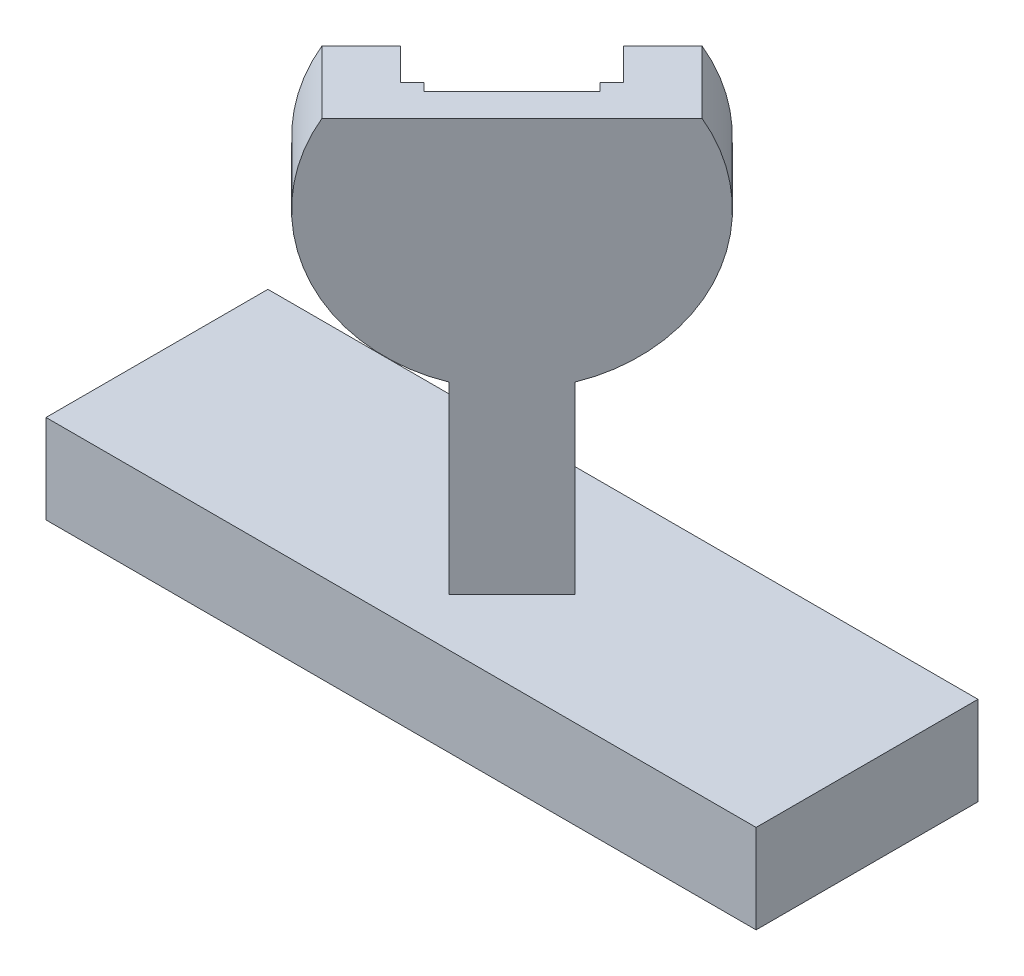
SolidWorks part; units mm, degrees
ref_plane "Front Plane" through (0, 0, 0) normal (0, 0, 1) x (1, 0, 0)
ref_plane "Top Plane" through (0, 0, 0) normal (0, 1, 0) x (1, 0, 0)
ref_plane "Right Plane" through (0, 0, 0) normal (1, 0, 0) x (0, 0, -1)
sketch "Sketch1" plane through (0, 0, 0) normal (0, 1, 0) x (1, 0, 0)
  line L0 (0, 7.1842) -> (-7.1842, 0)
  line L3 (-40.64, 12.7) -> (40.64, 12.7)
  line L4 (-40.64, 12.7) -> (-40.64, -12.7)
  line L5 (-40.64, -12.7) -> (40.64, -12.7)
  line L6 (40.64, 12.7) -> (40.64, -12.7)
  line L7 (-40.64, 12.7) -> (40.64, -12.7) construction
  line L8 (-40.64, -12.7) -> (40.64, 12.7) construction
  line L9 (-7.1842, 0) -> (0, -7.1842)
  line L10 (0, -7.1842) -> (7.1842, 0)
  line L11 (7.1842, 0) -> (0, 7.1842)
  line L12 (-7.1842, 0) -> (7.1842, 0) construction
  point P0 (0, 0)
  point P2 (0, 0)
  point P9 (0, 0)
  dimension "D1" = 81.28
  dimension "D2" = 25.4
  dimension "D3" = 10.16
extrude "Boss-Extrude1" add sketch "Sketch1" against normal blind 10.16 contours L10 L11 L0 L9 | L6 L3 L4 L5 L11 L10 L9 L0 region at (0, 0, 0) region at (0, 0, -11.8484)
extrude "Boss-Extrude2" add sketch "Sketch1<3>" along normal blind 25.4 contours L10 L11 L0 L9 region at (0, 0, 0)
sketch "Sketch1<3>" plane through (0, 0, 0) normal (0, 1, 0) x (1, 0, 0) same geometry as "Sketch1"
ref_plane "Plane1" through (3.5921, 0, 3.5921) normal (0.7071, 0, 0.7071) x (0.7071, 0, -0.7071)
sketch "Sketch3" plane through (3.5921, 0, 3.5921) normal (0.7071, 0, 0.7071) x (0.7071, 0, -0.7071)
  line L0 (-5.08, 25.4) -> (5.08, 25.4) construction
  line L1 (-5.08, 25.4) -> (5.08, 25.4)
  line L2 (0, 0) -> (0, 38.1635) construction
  line L3 (-9.0252, 47.1887) -> (0, 38.1635) construction
  line L4 (0, 38.1635) -> (9.0252, 47.1887) construction
  line L5 (-9.0252, 47.1887) -> (15.3928, 47.1887)
  line L6 (15.3928, 47.1887) -> (-15.3928, 47.1887)
  arc A0 (-9.0252, 47.1887) -> (9.0252, 47.1887) centre (0, 38.1635) ccw
  arc A1 (-15.3928, 47.1887) -> (15.3928, 47.1887) centre (0, 38.1635) ccw
  arc A2 (-12.6173, 50.7808) -> (12.6173, 50.7808) centre (0, 38.1635) ccw construction
  arc A3 (-7.1167, 47.1887) -> (7.1167, 47.1887) centre (0, 38.1635) ccw
  point P9 (0, 25.4)
  dimension "D4" = 1.27
  dimension "D1" = 12.7635
  dimension "D3" = 90
  dimension "D2" = 5.08
extrude "Boss-Extrude3" add sketch "Sketch3" against normal blind 10.16 contours L6 A1 A0 region at (-5.0379, 33.1082, 12.2221)
extrude "Boss-Extrude4" add sketch "Sketch3<3>" against normal blind 3.81 from surface contours L5 A0 | L6 A3 region at (-2.1149, 46.853, 9.2991) region at (3.5921, 37.549, 3.5921) starting at face at (3.5921, 25.5077, 3.5921)
sketch "Sketch3<3>" plane through (3.5921, 0, 3.5921) normal (0.7071, 0, 0.7071) x (0.7071, 0, -0.7071) same geometry as "Sketch3"
extrude "Boss-Extrude5" add sketch "Sketch3<4>" against normal blind 5.08 from surface contours A3 L5 A0 region at (-2.1149, 46.853, 9.2991) starting at face at (3.5921, 21.9122, 3.5921)
sketch "Sketch3<4>" plane through (3.5921, 0, 3.5921) normal (0.7071, 0, 0.7071) x (0.7071, 0, -0.7071) same geometry as "Sketch3"
sketch "Sketch6" plane through (-3.5921, 0, -3.5921) normal (-0.7071, 0, -0.7071) x (-0.7071, 0, 0.7071)
sketch "Sketch8" plane through (-3.5921, 0, -3.5921) normal (-0.7071, 0, -0.7071) x (-0.7071, 0, 0.7071)
  line L0 (0, 25.4) -> (0, 38.1635) construction
  line L1 (0, 38.1635) -> (17.8435, 38.1635) construction
  line L4 (-12.7635, 38.1635) -> (-17.8435, 38.1635) construction
  arc A0 (-9.0252, 47.1887) -> (9.0252, 47.1887) centre (0, 38.1635) ccw construction
  arc A1 (5.08, 21.0584) -> (15.3928, 47.1887) centre (0, 38.1635) ccw construction
  arc A2 (-9.0252, 47.1887) -> (9.0252, 47.1887) centre (0, 38.1635) ccw construction
  arc A3 (-15.3928, 47.1887) -> (-5.08, 21.0584) centre (0, 38.1635) ccw construction
  circle A4 centre (0, 38.1635) radius 15.3035 construction
  point P0 (15.3035, 38.1635)
  point P31 (-15.3035, 38.1635)
  point P32 (0, 0)
  point P33 (0, 0)
  point P34 (-15.3035, 38.1635)
hole_wizard "#8-32 Tapped Hole2" positions "Sketch8" profile "Sketch7" tap size "#8-32" standard "ANSI Inch"
sketch "Sketch7" plane through (-14.4133, 38.1635, 7.2291) normal (0, 1, 0) x (-0.7071, 0, 0.7071)
  line L0 (0, 0) -> (0, 8.6578)
  line L1 (0, 8.6578) -> (1.7272, 7.62)
  line L2 (1.7272, 7.62) -> (1.7272, 0)
  line L5 (1.7272, 0) -> (0, 0)
  line L10 (0, 8.6578) -> (-1.7272, 7.62) construction
  line L11 (0, -6.35) -> (0, 107.95) construction
  dimension "Tap Drill Dia." = 3.4544
  dimension "Tap Drill Depth" = 7.62
  dimension "Drill Angle" = 118
cosmetic thread "Hole Thread3" parameters "D1"=8.382, "D2"=4.1656
cosmetic thread "Hole Thread4" parameters "D1"=8.382, "D2"=4.1656
